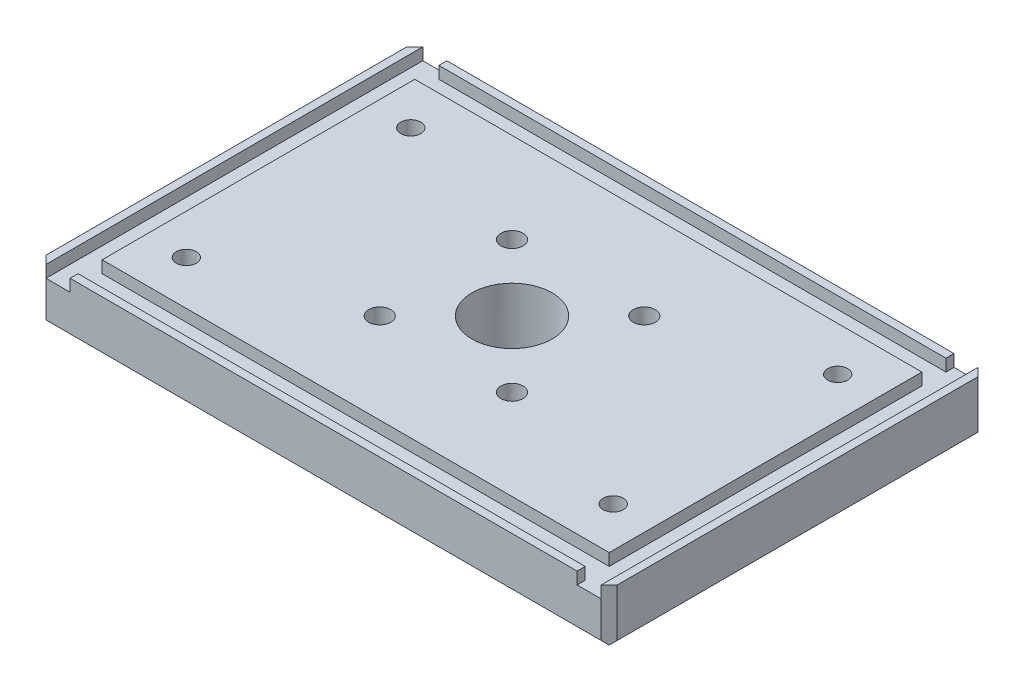
SolidWorks part; units mm, degrees
ref_plane "Front Plane" through (0, 0, 0) normal (0, 0, 1) x (1, 0, 0)
ref_plane "Top Plane" through (0, 0, 0) normal (0, 1, 0) x (1, 0, 0)
ref_plane "Right Plane" through (0, 0, 0) normal (1, 0, 0) x (0, 0, -1)
sketch "Sketch1" plane through (0, 0, 0) normal (0, 1, 0) x (1, 0, 0)
  line L1 (0, 0) -> (142.5, 0)
  line L2 (0, 0) -> (0, 94)
  line L3 (0, 94) -> (142.5, 94)
  line L4 (142.5, 0) -> (142.5, 94)
  dimension "D1" = 142.5
  dimension "D2" = 94
extrude "Boss-Extrude1" add sketch "Sketch1" along normal blind 15
sketch "Sketch2" plane through (0, 15, 0) normal (0, 1, 0) x (1, 0, 0)
  line L5 (8, 86) -> (134.5, 86)
  line L6 (8, 86) -> (8, 8)
  line L7 (8, 8) -> (134.5, 8)
  line L8 (134.5, 86) -> (134.5, 8)
  line L9 (0, 0) -> (142.5, 0) construction
  line L29 (134.5, 0) -> (140.5, 0)
  line L30 (134.5, 0) -> (134.5, 94)
  line L31 (134.5, 94) -> (140.5, 94)
  line L32 (140.5, 0) -> (140.5, 94)
  line L33 (142.5, 94) -> (0, 94) construction
  line L34 (142.5, 0) -> (142.5, 94) construction
  line L35 (8, 0) -> (2, 0)
  line L36 (8, 0) -> (8, 94)
  line L37 (8, 94) -> (2, 94)
  line L38 (2, 0) -> (2, 94)
  line L39 (8, 8) -> (134.5, 8)
  line L40 (8, 8) -> (8, 2)
  line L41 (8, 2) -> (134.5, 2)
  line L42 (134.5, 8) -> (134.5, 2)
  line L43 (8, 86) -> (134.5, 86)
  line L44 (8, 86) -> (8, 92)
  line L45 (8, 92) -> (134.5, 92)
  line L46 (134.5, 86) -> (134.5, 92)
  line L47 (0, 94) -> (0, 0) construction
  dimension "D1" = 6
  dimension "D2" = 6
  dimension "D3" = 2
  dimension "D4" = 2
  dimension "D5" = 6
  dimension "D6" = 2
  dimension "D7" = 2
  dimension "D8" = 6
extrude "Cut-Extrude2" cut sketch "Sketch2" against normal blind 3
chamfer "Chamfer1" distance 2 angle 45 4 edges at (0, 7.5, 0) (0, 7.5, -94) (142.5, 7.5, -94) (142.5, 7.5, 0)
sketch "Sketch6" plane through (0, 15, 0) normal (0, 1, 0) x (1, 0, 0)
  line L0 (134.5, 8) -> (134.5, 86) construction
  line L1 (8, 86) -> (134.5, 86) construction
  line L2 (8, 8) -> (134.5, 8) construction
  line L3 (8, 8) -> (8, 86) construction
  circle A0 centre (124.5, 75) radius 2.5
  circle A1 centre (18, 75) radius 2.5
  circle A2 centre (18, 19) radius 2.5
  circle A3 centre (124.5, 19) radius 2.5
  dimension "D1" = 5
  dimension "D2" = 10
  dimension "D3" = 11
  dimension "D4" = 11
  dimension "D5" = 10
extrude "Cut-Extrude7" cut sketch "Sketch6" against normal blind 10
sketch "Sketch7" plane through (0, 0, 0) normal (0, -1, 0) x (1, 0, 0)
  circle A0 centre (18, -19) radius 5
  circle A1 centre (124.5, -19) radius 5
  circle A2 centre (18, -75) radius 5
  circle A3 centre (124.5, -75) radius 5
  dimension "D1" = 10
extrude "Cut-Extrude8" cut sketch "Sketch7" against normal blind 5
chamfer "Chamfer2" distance 3 angle 45 4 edges at (142.5, 0, -47) (71.25, 0, 0) (0, 0, -47) (71.25, 0, -94)
sketch "Sketch8" plane through (0, 15, 0) normal (0, 1, 0) x (1, 0, 0)
  line L0 (8, 8) -> (8, 86) construction
  line L1 (8, 86) -> (134.5, 86) construction
  circle A0 centre (71.25, 47) radius 10
  point P4 (8, 47)
  point P7 (71.25, 86)
  dimension "D1" = 20
extrude "Cut-Extrude9" cut sketch "Sketch8" against normal up to surface (15 mm away) up to face at (71.25, 0, -47)
sketch "Sketch9" plane through (0, 15, 0) normal (0, 1, 0) x (1, 0, 0)
  line L0 (8, 86) -> (134.5, 86) construction
  line L1 (54.75, 63.5) -> (87.75, 63.5)
  line L2 (54.75, 63.5) -> (54.75, 30.5)
  line L3 (54.75, 30.5) -> (87.75, 30.5)
  line L4 (87.75, 63.5) -> (87.75, 30.5)
  line L5 (8, 8) -> (8, 86) construction
  circle A0 centre (54.75, 63.5) radius 2.75
  circle A1 centre (87.75, 63.5) radius 2.75
  circle A2 centre (87.75, 30.5) radius 2.75
  circle A3 centre (54.75, 30.5) radius 2.75
  point P6 (71.25, 86)
  point P7 (71.25, 63.5)
  point P10 (8, 47)
  point P11 (54.75, 47)
  dimension "D3" = 5.5
  dimension "D1" = 33
  dimension "D2" = 33
extrude "Cut-Extrude10" cut sketch "Sketch9" against normal through all contours L1 A0 L2 | L2 A0 L1 | L2 A3 L3 | L3 A3 L2 | L3 A2 L4 | L4 A2 L3 | L4 A1 L1 | L1 A1 L4
